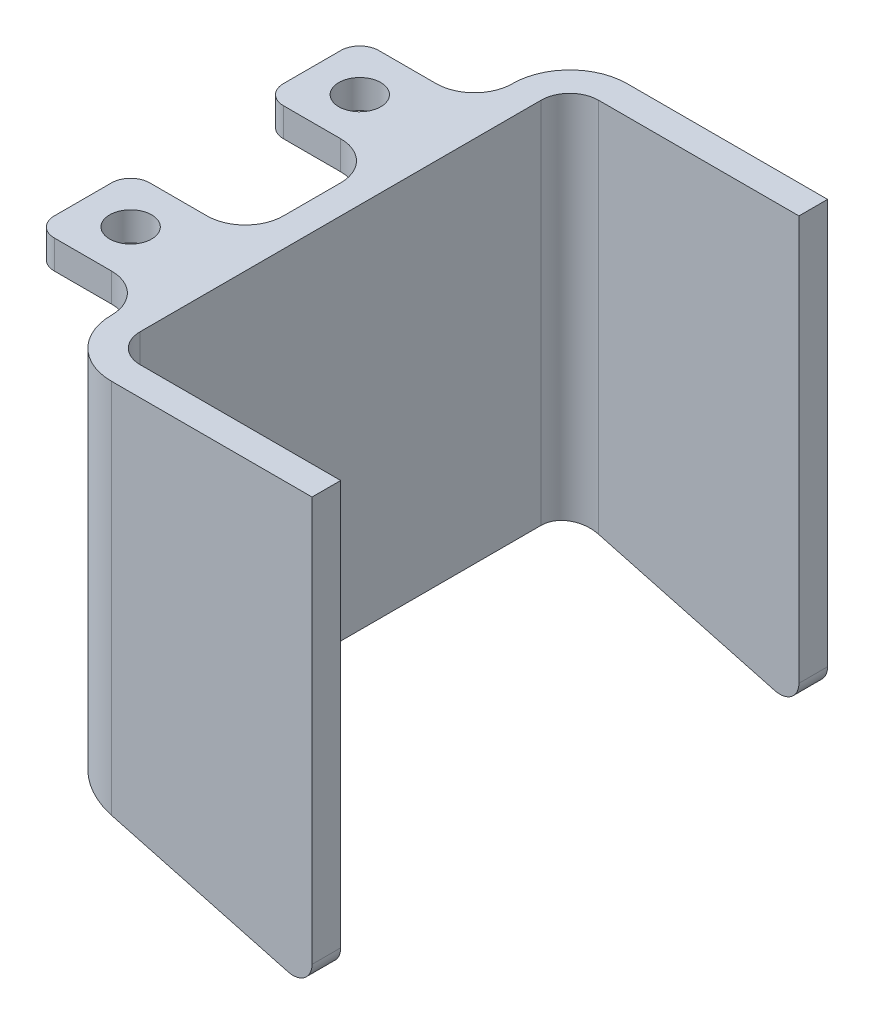
SolidWorks part; units mm, degrees
ref_plane "Front Plane" through (0, 0, 0) normal (0, 0, 1) x (1, 0, 0)
ref_plane "Top Plane" through (0, 0, 0) normal (0, 1, 0) x (1, 0, 0)
ref_plane "Right Plane" through (0, 0, 0) normal (1, 0, 0) x (0, 0, -1)
sketch "Sketch2" plane through (0, 0, 0) normal (0, 1, 0) x (1, 0, 0)
  line L0 (-6, 30) -> (6, 30)
  line L1 (6, 30) -> (6, 24)
  line L2 (6, 24) -> (2, 24)
  line L3 (2, 24) -> (2, -24)
  line L4 (2, -24) -> (6, -24)
  line L5 (6, -24) -> (6, -30)
  line L6 (6, -30) -> (-6, -30)
  line L7 (-6, -30) -> (-6, -24)
  line L8 (-6, -24) -> (-2, -24)
  line L9 (-2, -24) -> (-2, 24)
  line L10 (-2, 24) -> (-6, 24)
  line L11 (-6, 24) -> (-6, 30)
  dimension "D2" = 60
  dimension "D3" = 6
  dimension "D4" = 4
sketch "Sketch3" plane through (0, 0, 0) normal (0, 1, 0) x (1, 0, 0)
  line L5 (-8, 24) -> (-8, -24) construction
  line L6 (-8, 24) -> (-29, 24)
  line L7 (-32, 21) -> (-32, -21)
  line L8 (-29, -24) -> (-8, -24)
  line L16 (-8, 27) -> (-29, 27)
  line L17 (-35, 21) -> (-35, -21)
  line L18 (-29, -27) -> (-8, -27)
  line L19 (-8, 27) -> (-8, 24)
  line L20 (-8, -24) -> (-8, -27)
  arc A10 (-29, -24) -> (-32, -21) centre (-29, -21) cw
  arc A11 (-32, 21) -> (-29, 24) centre (-29, 21) cw
  arc A12 (-35, 21) -> (-29, 27) centre (-29, 21) cw
  arc A13 (-29, -27) -> (-35, -21) centre (-29, -21) cw
  point P2 (-8, 0)
  point P9 (-32, 24)
  dimension "D4" = 3
  dimension "D1" = 2
  dimension "D2" = 48
  dimension "D3" = 24
  dimension "D5" = 3
extrude "Boss-Extrude1" add sketch "Sketch3" along normal blind 45
sketch "Sketch4" plane through (0, 45, 0) normal (0, 1, 0) x (1, 0, 0)
  line L0 (-35, 21) -> (-35, -21) construction
  line L1 (-47, 17) -> (-35, 17)
  line L2 (-47, 17) -> (-47, 7)
  line L3 (-47, 7) -> (-35, 7)
  line L4 (-35, 17) -> (-35, 7)
  line L6 (-35, -7) -> (-47, -7)
  line L7 (-35, -7) -> (-35, -17)
  line L8 (-35, -17) -> (-47, -17)
  line L9 (-47, -7) -> (-47, -17)
  circle A0 centre (-42, 12) radius 2.2
  circle A1 centre (-42, -12) radius 2.2
  point P8 (-47, 12)
  point P16 (-47, -12)
  dimension "D2" = 4.4
  dimension "D6" = 4.4
  dimension "D1" = 5
  dimension "D3" = 12
  dimension "D4" = 10
  dimension "D5" = 10
  dimension "D7" = 12
  dimension "D8" = 12
extrude "Boss-Extrude2" add sketch "Sketch4" against normal blind 3
fillet "Fillet1" radius 4 4 edges at (-35, 43.5, 17) (-35, 43.5, 7) (-35, 43.5, -17) (-35, 43.5, -7)
fillet "Fillet2" radius 2 2 edges at (-35, 42, 12) (-35, 42, -12)
fillet "Fillet3" radius 2 4 edges at (-47, 43.5, 17) (-47, 43.5, 7) (-47, 43.5, -7) (-47, 43.5, -17)
sketch "Sketch5" plane through (0, 0, 0) normal (0, 0, 1) x (1, 0, 0)
  line L0 (-8, 0) -> (-35, 7.2346)
  line L1 (-35, 40) -> (-35, 0) construction
  line L2 (-35, 7.2346) -> (-35, 0)
  line L3 (-35, 0) -> (-8, 0)
  dimension "D1" = 15
extrude "Cut-Extrude1" cut sketch "Sketch5" against normal through all both and the other way through all
fillet "Fillet4" radius 2 2 edges at (-8, 0, -25.5) (-8, 0, 25.5)
